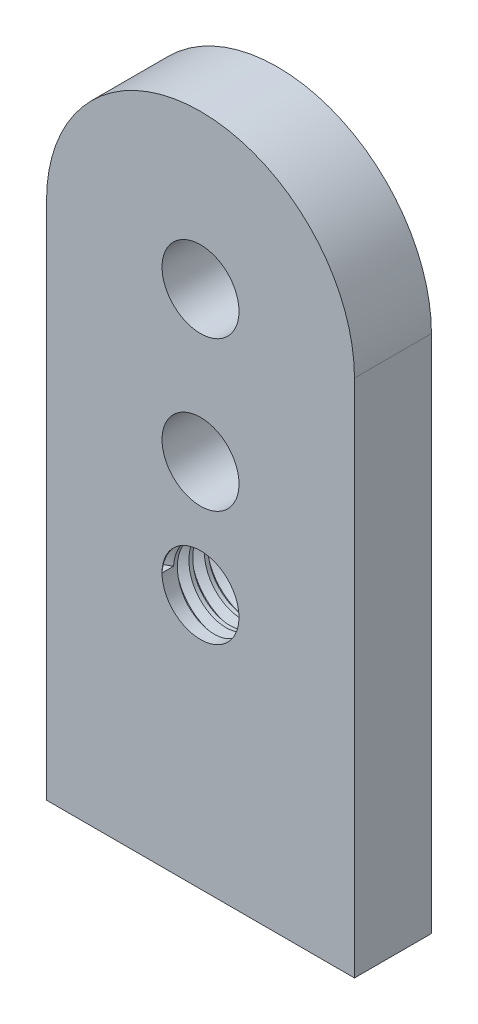
SolidWorks part; units mm, degrees
material "1060 Alloy"
ref_plane "Front Plane" through (0, 0, 0) normal (0, 0, 1) x (1, 0, 0)
ref_plane "Top Plane" through (0, 0, 0) normal (0, 1, 0) x (1, 0, 0)
ref_plane "Right Plane" through (0, 0, 0) normal (1, 0, 0) x (0, 0, -1)
sketch "Sketch1" plane through (0, 0, 0) normal (0, 0, 1) x (1, 0, 0)
  line L0 (0, 0) -> (0, 11.4806) construction
  line L1 (-12.7, 0) -> (12.7, 0)
  line L2 (-12.7, 0) -> (-12.7, 42.8625)
  line L4 (12.7, 0) -> (12.7, 42.8625)
  arc A0 (12.7, 42.8625) -> (-12.7, 42.8625) centre (0, 42.8625) ccw
  circle A1 centre (0, 42.8625) radius 3.175
  circle A2 centre (0, 21.0058) radius 3.175
  circle A3 centre (0, 30.5308) radius 3.175
  circle A4 centre (0, 42.8625) radius 6.35 construction
  point P7 (0, 55.5625)
  dimension "D3" = 6.35
  dimension "D4" = 6.35
  dimension "D6" = 6.35
  dimension "D8" = 12.7
  dimension "D1" = 42.8625
  dimension "D2" = 25.4
  dimension "D5" = 21.0058
  dimension "D7" = 9.525
extrude "Boss-Extrude1" add sketch "Sketch1" along normal mid plane 6.35
thread "Thread1" pitch 1.27 method cut profile "Thread Profile1" start angle 0, offset 0, length 0, pitch 1.27, diameter 6.35
ref_plane "Plane1" through (-3.175, 21.0058, 3.175) normal (0, -1, 0) x (-1, 0, 0)
sketch "Thread Profile1" plane through (-3.175, 21.0058, 3.175) normal (0, -1, 0) x (-1, 0, 0)
  line L0 (0, 0) -> (0, 1.27) construction
  line L1 (0, 0) -> (0.6874, 0.3969)
  line L2 (0.6874, 0.3969) -> (0.6874, 0.5556)
  line L3 (0.6874, 0.5556) -> (0, 0.9525)
  line L4 (0.6874, 0.4762) -> (0, 0.4762) construction
  line L11 (0, 0) -> (0, 0.9525)
  point P2 (0, 0)
  dimension "Pitch" = 1.27
  dimension "Profile_Angle" = 60
  dimension "Profile_Land" = 0.1588
  dimension "Profile_Height" = 0.6874
